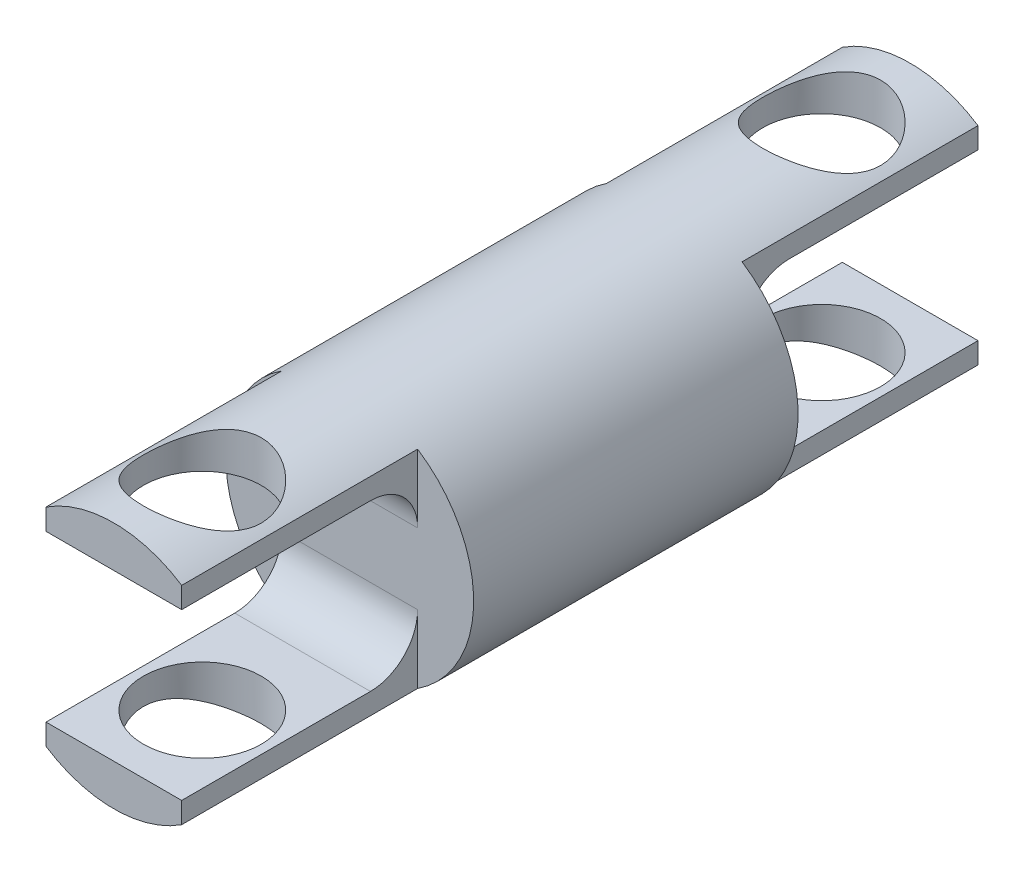
SolidWorks part; units mm, degrees
ref_plane "Płaszczyzna przednia" through (0, 0, 0) normal (0, 0, 1) x (1, 0, 0)
ref_plane "Płaszczyzna górna" through (0, 0, 0) normal (0, 1, 0) x (1, 0, 0)
ref_plane "Płaszczyzna prawa" through (0, 0, 0) normal (1, 0, 0) x (0, 0, -1)
sketch "Szkic1" plane through (0, 0, 0) normal (0, 0, 1) x (1, 0, 0)
  circle A0 centre (0, 0) radius 21
  dimension "D1" = 42
extrude "Dodanie-wyciągnięcie1" add sketch "Szkic1" along normal blind 27.5 contours A0
sketch "Szkic6" plane through (0, 0, 27.5) normal (0, 0, 1) x (1, 0, 0)
  line L0 (-11.5, 17.5713) -> (-11.5, 14)
  line L1 (-11.5, 14) -> (11.5, 14)
  line L2 (11.5, 14) -> (11.5, 17.5713)
  line L3 (0, 0) -> (13.4968, 0) construction
  line L4 (11.5, -14) -> (11.5, -17.5713)
  line L5 (-11.5, -14) -> (11.5, -14)
  line L6 (-11.5, -17.5713) -> (-11.5, -14)
  circle A0 centre (0, 0) radius 21 construction
  arc A1 (-11.5, -17.5713) -> (11.5, -17.5713) centre (0, 0) ccw
  arc A2 (11.5, 17.5713) -> (-11.5, 17.5713) centre (0, 0) ccw
  dimension "D1" = 14
  dimension "D2" = 11.5
  dimension "D3" = 11.5
extrude "Dodanie-wyciągnięcie4" add sketch "Szkic6" along normal blind 40
sketch "Szkic7" plane through (0, -14, 0) normal (0, 1, 0) x (1, 0, 0)
  line L0 (11.5, -67.5) -> (-11.5, -67.5) construction
  line L1 (11.5, -27.5) -> (-11.5, -27.5) construction
  circle A0 centre (0, -52.5) radius 10
  point P7 (0, -27.5)
  dimension "D1" = 20
  dimension "D2" = 15
extrude "Wytnij-wyciągnięcie1" cut sketch "Szkic7" along normal blind 40 and the other way up to next
fillet "Zaokrąglenie1" radius 8 2 edges at (0, -14, 27.5) (0, 14, 27.5)
mirror "Lustro2" about plane through (0, 0, 0) normal (0, 0, 1) of "Dodanie-wyciągnięcie1", "Zaokrąglenie1", "Wytnij-wyciągnięcie1", "Dodanie-wyciągnięcie4"
